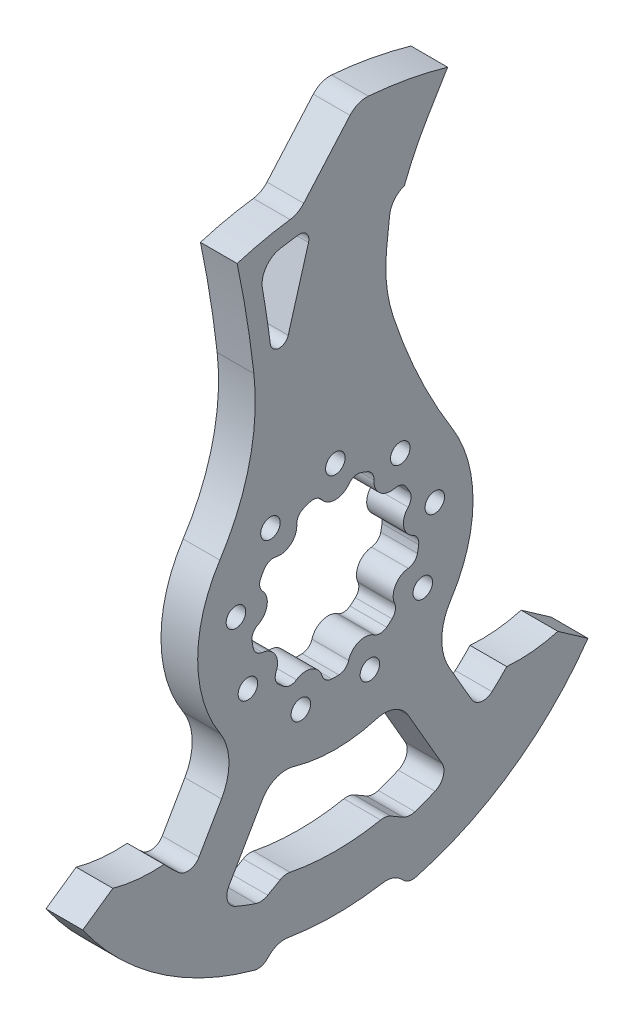
SolidWorks part; units mm, degrees
material "AR500"
ref_plane "Front Plane" through (0, 0, 0) normal (0, 0, 1) x (1, 0, 0)
ref_plane "Top Plane" through (0, 0, 0) normal (0, 1, 0) x (1, 0, 0)
ref_plane "Right Plane" through (0, 0, 0) normal (1, 0, 0) x (0, 0, -1)
other "Center of Mass"
sketch "Sketch1" plane through (0, 0, 0) normal (1, 0, 0) x (0, 0, -1)
  circle A0 centre (0, 0) radius 139.7 construction
  circle A1 centre (0, 0) radius 106.68 construction
  circle A2 centre (0, 0) radius 44.45 construction
  dimension "D1" = 279.4
  dimension "D2" = 33.02
  dimension "D3" = 88.9
sketch "Sketch2" plane through (0, 0, 0) normal (1, 0, 0) x (0, 0, -1)
  line L0 (0, 0) -> (38.858, 134.187) construction
  line L1 (38.858, 134.187) -> (32.2885, 123.3181)
  line L2 (0, 0) -> (0, 61.679) construction
  line L3 (7.5549, 139.4956) -> (-12.8644, 116.1296)
  line L4 (-33.9764, 111.7908) -> (-39.3372, 137.2171) construction
  line L5 (23.88, 106.192) -> (16.7676, 87.8077) construction
  line L6 (23.88, 106.192) -> (19.2337, 104.1379)
  line L7 (19.2337, 104.1379) -> (17.7417, 90.2907)
  line L8 (-33.9764, 111.7908) -> (-3.6464, 121.009) construction
  line L10 (0, -100.33) -> (0, 0) construction
  line L11 (-20.0866, -98.2987) -> (-25.4, -103.6121)
  line L16 (-49.9001, -64.1593) -> (-32.7957, -34.5337)
  line L17 (87.3871, -61.1891) -> (76.9839, -53.9047)
  line L18 (-87.3871, -61.1891) -> (-76.9839, -53.9047)
  line L19 (49.9001, -64.1593) -> (32.7957, -34.5337)
  line L24 (53.8815, -53.8815) -> (0, 0) construction
  line L25 (20.0866, -98.2987) -> (25.4, -103.6121)
  circle A0 centre (0, 0) radius 139.7 construction
  arc A1 (38.858, 134.187) -> (7.5549, 139.4956) centre (0, 0) ccw
  arc A2 (-12.8644, 116.1296) -> (-33.9764, 111.7908) centre (0, 0) ccw
  arc A3 (32.2885, 123.3181) -> (23.88, 106.192) centre (125.9607, 66.6999) ccw
  arc A4 (40.4523, 25.1346) -> (32.7957, -34.5337) centre (0, 0) cw
  circle A5 centre (0, 0) radius 44.45 construction
  arc A6 (19.9828, 69.006) -> (17.7417, 90.2907) centre (68.2493, 84.8485) cw
  arc A7 (-33.9764, 111.7908) -> (-28.182, 75.8993) centre (-406.7808, 33.191) cw
  arc A8 (-28.182, 75.8993) -> (-39.9622, 25.9068) centre (-103.9018, 67.3576) cw
  arc A9 (-39.9622, 25.9068) -> (-32.7957, -34.5337) centre (0, 0) ccw
  arc A10 (-87.3871, -61.1891) -> (-25.4, -103.6121) centre (0, 0) ccw
  circle A11 centre (0, 0) radius 106.68 construction
  arc A18 (-76.9839, -53.9047) -> (-59.2852, -55.6031) centre (-63.357, -4.9665) ccw
  arc A19 (-59.2852, -55.6031) -> (-49.9001, -64.1593) centre (0, 0) ccw
  arc A20 (-20.0866, -98.2987) -> (20.0866, -98.2987) centre (0, 0) ccw
  arc A21 (59.2852, -55.6031) -> (49.9001, -64.1593) centre (0, 0) cw
  arc A22 (76.9839, -53.9047) -> (59.2852, -55.6031) centre (63.357, -4.9665) cw
  arc A23 (87.3871, -61.1891) -> (25.4, -103.6121) centre (0, 0) cw
  arc A25 (19.9828, 69.006) -> (40.4523, 25.1346) centre (213.0489, 132.3758) ccw
  dimension "D4" = 22.86
  dimension "D11" = 95.25
  dimension "D13" = 50.8
  dimension "D14" = 381
  dimension "D16" = 76.2
  dimension "D19" = 6.35
  dimension "D21" = 55
  dimension "D26" = 17.78
  dimension "D22" = 25.4
  dimension "D23" = 50.8
  dimension "D27" = 12.7
  dimension "D29" = 203.2
  dimension "D1" = 15
  dimension "D2" = 16.15
  dimension "D3" = 10
  dimension "D5" = 31.75
  dimension "D6" = 12.7
  dimension "D7" = 31.75
  dimension "D8" = 5
  dimension "D9" = 45
  dimension "D10" = 10
  dimension "D12" = 5.08
  dimension "D15" = 85
  dimension "D17" = 76.2
  dimension "D18" = 25.4
  dimension "D20" = 45
  dimension "D24" = 12.7
  dimension "D25" = 45
  dimension "D28" = 30
extrude "Boss-Extrude1" add sketch "Sketch2" along normal mid plane 12.7
sketch "Sketch3" plane through (6.35, 0, 0) normal (1, 0, 0) x (0, 0, -1)
  line L1 (-9.2851, 105.7206) -> (-16.3113, 81.4575)
  line L2 (17.7417, 90.2907) -> (19.2337, 104.1379) construction
  line L3 (-3.258, 62.2657) -> (5.5274, 106.8394) construction
  line L4 (19.2337, 104.1379) -> (-8.1789, 109.5409) construction
  arc A0 (-12.8644, 116.1296) -> (-33.9764, 111.7908) centre (0, 0) ccw construction
  arc A1 (-28.182, 75.8993) -> (-33.9764, 111.7908) centre (-406.7808, 33.191) ccw construction
  arc A2 (-9.2851, 105.7206) -> (-12.6998, 109.7577) centre (-12.3348, 106.6038) ccw
  arc A3 (-12.8644, 116.1296) -> (-33.9764, 111.7908) centre (0, 0) ccw construction
  arc A4 (-28.182, 75.8993) -> (-33.9764, 111.7908) centre (-406.7808, 33.191) ccw construction
  arc A5 (-12.6998, 109.7577) -> (-26.5758, 107.2463) centre (0, 0) ccw
  arc A6 (-22.5107, 81.941) -> (-26.5758, 107.2463) centre (-406.7808, 33.191) ccw
  arc A7 (-21.8721, 76.6111) -> (-26.5758, 107.2463) centre (-406.7808, 33.191) ccw construction
  arc A8 (-12.1653, 109.8182) -> (-26.5758, 107.2463) centre (0, 0) ccw construction
  arc A14 (-22.5107, 81.941) -> (-16.3113, 81.4575) centre (-19.361, 82.3406) ccw
  point P18 (19.2337, 104.1379)
  dimension "D5" = 3.175
  dimension "D7" = 3.175
  dimension "D3" = 10
  dimension "D4" = 27.94
  dimension "D1" = 6.35
extrude "Cut-Extrude1" cut sketch "Sketch3" against normal through all
fillet "Fillet1" radius 7.62 6 edges at (0, 104.1379, -19.2337) (0, 107.2463, 26.5758) (0, 139.4956, -7.5549) (0, 116.1296, 12.8644) (0, -98.2987, -20.0866) (0, -98.2987, 20.0866)
fillet "Fillet4" radius 19.05 2 edges at (0, -34.5337, -32.7957) (0, -34.5337, 32.7957)
fillet "Fillet2" radius 4.572 4 edges at (0, -103.6121, 25.4) (0, -103.6121, -25.4) (0, -64.1593, -49.9001) (0, -64.1593, 49.9001)
sketch "Sketch4" plane through (6.35, 0, 0) normal (1, 0, 0) x (0, 0, -1)
  line L0 (-21.1843, -46.1721) -> (-39.646, -78.1487)
  line L1 (-39.3687, -45.9185) -> (-47.1846, -59.4559) construction
  line L2 (0, -81.28) -> (0, -50.8)
  line L3 (-25.3274, -83.8901) -> (-17.5035, -79.373)
  line L4 (-11.6185, -94.3061) -> (-25.8749, -102.5371) construction
  arc A0 (-39.646, -78.1487) -> (-25.3274, -83.8901) centre (0, 0) ccw
  arc A1 (0, -50.8) -> (-21.1843, -46.1721) centre (0, 0) cw
  circle A2 centre (0, 0) radius 44.45 construction
  circle A3 centre (0, 0) radius 106.68 construction
  arc A4 (-17.5035, -79.373) -> (0, -81.28) centre (0, 0) ccw
  arc A5 (-16.2916, -98.9984) -> (16.2916, -98.9984) centre (0, 0) ccw construction
  arc A6 (-87.3871, -61.1891) -> (-27.9851, -102.9439) centre (0, 0) ccw construction
  arc A7 (-16.2916, -98.9984) -> (-22.9171, -101.1292) centre (-17.5289, -106.5173) ccw construction
  dimension "D1" = 50.8
  dimension "D3" = 19.05
  dimension "D4" = 19.05
  dimension "D2" = 15.875
  dimension "D5" = 30
  dimension "D6" = 15.875
extrude "Cut-Extrude2" cut sketch "Sketch4" against normal through all
mirror "Mirror1" about plane through (-6.35, -81.28, 0) normal (0, 0, -1) of "Cut-Extrude2"
fillet "Fillet3" radius 5.08 6 edges at (0, -78.1487, -39.646) (0, -83.8901, -25.3274) (0, -79.373, -17.5035) (0, -79.373, 17.5035) (0, -83.8901, 25.3274) (0, -78.1487, 39.646)
fillet "Fillet5" radius 9.525 2 edges at (0, -46.1721, -21.1843) (0, -46.1721, 21.1843)
ref_axis "Axis2" through (-6.985, 0, 0) along (1, 0, 0)
sketch "Sketch5" plane through (-6.35, 0, 0) normal (-1, 0, 0) x (0, 0, 1)
  arc A36 (-24.1266, 15.3113) -> (-25.3233, 13.2386) centre (0, 0) ccw construction
  arc A37 (-20.6919, 16.6942) -> (-24.1266, 15.3113) centre (-21.4459, 13.6101) ccw construction
  arc A38 (-20.6919, 16.6942) -> (-12.8475, 23.2765) centre (-19.184, 22.8626) ccw construction
  arc A39 (-10.8892, 26.4189) -> (-12.8475, 23.2765) centre (-9.6793, 23.4834) ccw construction
  arc A40 (-8.6401, 27.2374) -> (-10.8892, 26.4189) centre (0, 0) ccw construction
  arc A41 (-5.1201, 26.089) -> (-8.6401, 27.2374) centre (-7.6801, 24.2111) ccw construction
  arc A42 (-5.1201, 26.089) -> (5.1201, 26.089) centre (0, 29.845) ccw construction
  arc A43 (8.6401, 27.2374) -> (5.1201, 26.089) centre (7.6801, 24.2111) ccw construction
  arc A44 (10.8892, 26.4189) -> (8.6401, 27.2374) centre (0, 0) ccw construction
  arc A45 (12.8475, 23.2765) -> (10.8892, 26.4189) centre (9.6793, 23.4834) ccw construction
  arc A46 (12.8475, 23.2765) -> (20.6919, 16.6942) centre (19.184, 22.8626) ccw construction
  arc A47 (24.1266, 15.3113) -> (20.6919, 16.6942) centre (21.4459, 13.6101) ccw construction
  arc A48 (25.3233, 13.2386) -> (24.1266, 15.3113) centre (0, 0) ccw construction
  arc A49 (24.8036, 9.5726) -> (25.3233, 13.2386) centre (22.5096, 11.7677) ccw construction
  arc A50 (24.8036, 9.5726) -> (26.5818, -0.512) centre (29.3916, 5.1825) ccw construction
  arc A51 (28.324, -3.7791) -> (26.5818, -0.512) centre (25.1769, -3.3592) ccw construction
  arc A52 (27.9084, -6.1361) -> (28.324, -3.7791) centre (0, 0) ccw construction
  arc A53 (25.1538, -8.6104) -> (27.9084, -6.1361) centre (24.8075, -5.4543) ccw construction
  arc A54 (25.1538, -8.6104) -> (20.0337, -17.4786) centre (25.8465, -14.9225) ccw construction
  arc A55 (19.2682, -21.1013) -> (20.0337, -17.4786) centre (17.1273, -18.7567) ccw construction
  arc A56 (17.4348, -22.6397) -> (19.2682, -21.1013) centre (0, 0) ccw construction
  arc A57 (13.7343, -22.7645) -> (17.4348, -22.6397) centre (15.4976, -20.1242) ccw construction
  arc A58 (13.7343, -22.7645) -> (4.1117, -26.2669) centre (10.2076, -28.0451) ccw construction
  arc A59 (1.1967, -28.5499) -> (4.1117, -26.2669) centre (1.0637, -25.3777) ccw construction
  arc A60 (-1.1967, -28.5499) -> (1.1967, -28.5499) centre (0, 0) ccw construction
  arc A61 (-4.1117, -26.2669) -> (-1.1967, -28.5499) centre (-1.0637, -25.3777) ccw construction
  arc A62 (-4.1117, -26.2669) -> (-13.7343, -22.7645) centre (-10.2076, -28.0451) ccw construction
  arc A63 (-17.4348, -22.6397) -> (-13.7343, -22.7645) centre (-15.4976, -20.1242) ccw construction
  arc A64 (-19.2682, -21.1013) -> (-17.4348, -22.6397) centre (0, 0) ccw construction
  arc A65 (-20.0337, -17.4786) -> (-19.2682, -21.1013) centre (-17.1273, -18.7567) ccw construction
  arc A66 (-20.0337, -17.4786) -> (-25.1538, -8.6104) centre (-25.8465, -14.9225) ccw construction
  arc A67 (-27.9084, -6.1361) -> (-25.1538, -8.6104) centre (-24.8075, -5.4543) ccw construction
  arc A68 (-28.324, -3.7791) -> (-27.9084, -6.1361) centre (0, 0) ccw construction
  arc A69 (-26.5818, -0.512) -> (-28.324, -3.7791) centre (-25.1769, -3.3592) ccw construction
  arc A70 (-26.5818, -0.512) -> (-24.8036, 9.5726) centre (-29.3916, 5.1825) ccw construction
  arc A71 (-25.3233, 13.2386) -> (-24.8036, 9.5726) centre (-22.5096, 11.7677) ccw construction
  arc A146 (-24.1266, 15.3113) -> (-25.3233, 13.2386) centre (0, 0) ccw construction
  arc A147 (-20.6919, 16.6942) -> (-24.1266, 15.3113) centre (-21.4459, 13.6101) ccw construction
  arc A148 (-20.6919, 16.6942) -> (-12.8475, 23.2765) centre (-19.184, 22.8626) ccw construction
  arc A149 (-10.8892, 26.4189) -> (-12.8475, 23.2765) centre (-9.6793, 23.4834) ccw construction
  arc A150 (-8.6401, 27.2374) -> (-10.8892, 26.4189) centre (0, 0) ccw construction
  arc A151 (-5.1201, 26.089) -> (-8.6401, 27.2374) centre (-7.6801, 24.2111) ccw construction
  arc A152 (-5.1201, 26.089) -> (5.1201, 26.089) centre (0, 29.845) ccw construction
  arc A153 (8.6401, 27.2374) -> (5.1201, 26.089) centre (7.6801, 24.2111) ccw construction
  arc A154 (10.8892, 26.4189) -> (8.6401, 27.2374) centre (0, 0) ccw construction
  arc A155 (12.8475, 23.2765) -> (10.8892, 26.4189) centre (9.6793, 23.4834) ccw construction
  arc A156 (12.8475, 23.2765) -> (20.6919, 16.6942) centre (19.184, 22.8626) ccw construction
  arc A157 (24.1266, 15.3113) -> (20.6919, 16.6942) centre (21.4459, 13.6101) ccw construction
  arc A158 (25.3233, 13.2386) -> (24.1266, 15.3113) centre (0, 0) ccw construction
  arc A159 (24.8036, 9.5726) -> (25.3233, 13.2386) centre (22.5096, 11.7677) ccw construction
  arc A160 (24.8036, 9.5726) -> (26.5818, -0.512) centre (29.3916, 5.1825) ccw construction
  arc A161 (28.324, -3.7791) -> (26.5818, -0.512) centre (25.1769, -3.3592) ccw construction
  arc A162 (27.9084, -6.1361) -> (28.324, -3.7791) centre (0, 0) ccw construction
  arc A163 (25.1538, -8.6104) -> (27.9084, -6.1361) centre (24.8075, -5.4543) ccw construction
  arc A164 (25.1538, -8.6104) -> (20.0337, -17.4786) centre (25.8465, -14.9225) ccw construction
  arc A165 (19.2682, -21.1013) -> (20.0337, -17.4786) centre (17.1273, -18.7567) ccw construction
  arc A166 (17.4348, -22.6397) -> (19.2682, -21.1013) centre (0, 0) ccw construction
  arc A167 (13.7343, -22.7645) -> (17.4348, -22.6397) centre (15.4976, -20.1242) ccw construction
  arc A168 (13.7343, -22.7645) -> (4.1117, -26.2669) centre (10.2076, -28.0451) ccw construction
  arc A169 (1.1967, -28.5499) -> (4.1117, -26.2669) centre (1.0637, -25.3777) ccw construction
  arc A170 (-1.1967, -28.5499) -> (1.1967, -28.5499) centre (0, 0) ccw construction
  arc A171 (-4.1117, -26.2669) -> (-1.1967, -28.5499) centre (-1.0637, -25.3777) ccw construction
  arc A172 (-4.1117, -26.2669) -> (-13.7343, -22.7645) centre (-10.2076, -28.0451) ccw construction
  arc A173 (-17.4348, -22.6397) -> (-13.7343, -22.7645) centre (-15.4976, -20.1242) ccw construction
  arc A174 (-19.2682, -21.1013) -> (-17.4348, -22.6397) centre (0, 0) ccw construction
  arc A175 (-20.0337, -17.4786) -> (-19.2682, -21.1013) centre (-17.1273, -18.7567) ccw construction
  arc A176 (-20.0337, -17.4786) -> (-25.1538, -8.6104) centre (-25.8465, -14.9225) ccw construction
  arc A177 (-27.9084, -6.1361) -> (-25.1538, -8.6104) centre (-24.8075, -5.4543) ccw construction
  arc A178 (-28.324, -3.7791) -> (-27.9084, -6.1361) centre (0, 0) ccw construction
  arc A179 (-26.5818, -0.512) -> (-28.324, -3.7791) centre (-25.1769, -3.3592) ccw construction
  arc A180 (-26.5818, -0.512) -> (-24.8036, 9.5726) centre (-29.3916, 5.1825) ccw construction
  arc A181 (-25.3233, 13.2386) -> (-24.8036, 9.5726) centre (-22.5096, 11.7677) ccw construction
  arc A182 (-24.5555, 15.5835) -> (-25.7735, 13.474) centre (0, 0) ccw
  arc A183 (-25.7735, 13.474) -> (-25.1706, 9.2214) centre (-22.5096, 11.7677) ccw
  arc A184 (-26.8066, -0.0564) -> (-25.1706, 9.2214) centre (-29.3916, 5.1825) ccw
  arc A185 (-26.8066, -0.0564) -> (-28.8275, -3.8463) centre (-25.1769, -3.3592) ccw
  arc A186 (-28.8275, -3.8463) -> (-28.4045, -6.2452) centre (0, 0) ccw
  arc A187 (-28.4045, -6.2452) -> (-25.2092, -9.1154) centre (-24.8075, -5.4543) ccw
  arc A188 (-20.4988, -17.2742) -> (-25.2092, -9.1154) centre (-25.8465, -14.9225) ccw
  arc A189 (-20.4988, -17.2742) -> (-19.6108, -21.4764) centre (-17.1273, -18.7567) ccw
  arc A190 (-19.6108, -21.4764) -> (-17.7448, -23.0422) centre (0, 0) ccw
  arc A191 (-17.7448, -23.0422) -> (-13.4521, -23.187) centre (-15.4976, -20.1242) ccw
  arc A192 (-4.5993, -26.4091) -> (-13.4521, -23.187) centre (-10.2076, -28.0451) ccw
  arc A193 (-4.5993, -26.4091) -> (-1.2179, -29.0575) centre (-1.0637, -25.3777) ccw
  arc A194 (-1.2179, -29.0575) -> (1.2179, -29.0575) centre (0, 0) ccw
  arc A195 (1.2179, -29.0575) -> (4.5993, -26.4091) centre (1.0637, -25.3777) ccw
  arc A196 (13.4521, -23.187) -> (4.5993, -26.4091) centre (10.2076, -28.0451) ccw
  arc A197 (13.4521, -23.187) -> (17.7448, -23.0422) centre (15.4976, -20.1242) ccw
  arc A198 (17.7448, -23.0422) -> (19.6108, -21.4764) centre (0, 0) ccw
  arc A199 (19.6108, -21.4764) -> (20.4988, -17.2742) centre (17.1273, -18.7567) ccw
  arc A200 (25.2092, -9.1154) -> (20.4988, -17.2742) centre (25.8465, -14.9225) ccw
  arc A201 (25.2092, -9.1154) -> (28.4045, -6.2452) centre (24.8075, -5.4543) ccw
  arc A202 (28.4045, -6.2452) -> (28.8275, -3.8463) centre (0, 0) ccw
  arc A203 (28.8275, -3.8463) -> (26.8066, -0.0564) centre (25.1769, -3.3592) ccw
  arc A204 (25.1706, 9.2214) -> (26.8066, -0.0564) centre (29.3916, 5.1825) ccw
  arc A205 (25.1706, 9.2214) -> (25.7735, 13.474) centre (22.5096, 11.7677) ccw
  arc A206 (25.7735, 13.474) -> (24.5555, 15.5835) centre (0, 0) ccw
  arc A207 (24.5555, 15.5835) -> (20.5713, 17.1877) centre (21.4459, 13.6101) ccw
  arc A208 (13.3544, 23.2434) -> (20.5713, 17.1877) centre (19.184, 22.8626) ccw
  arc A209 (13.3544, 23.2434) -> (11.0827, 26.8885) centre (9.6793, 23.4834) ccw
  arc A210 (11.0827, 26.8885) -> (8.7937, 27.7217) centre (0, 0) ccw
  arc A211 (8.7937, 27.7217) -> (4.7105, 26.3895) centre (7.6801, 24.2111) ccw
  arc A212 (-4.7105, 26.3895) -> (4.7105, 26.3895) centre (0, 29.845) ccw
  arc A213 (-4.7105, 26.3895) -> (-8.7937, 27.7217) centre (-7.6801, 24.2111) ccw
  arc A214 (-8.7937, 27.7217) -> (-11.0827, 26.8885) centre (0, 0) ccw
  arc A215 (-11.0827, 26.8885) -> (-13.3544, 23.2434) centre (-9.6793, 23.4834) ccw
  arc A216 (-20.5713, 17.1877) -> (-13.3544, 23.2434) centre (-19.184, 22.8626) ccw
  arc A217 (-20.5713, 17.1877) -> (-24.5555, 15.5835) centre (-21.4459, 13.6101) ccw
  dimension "D1" = 0.508
extrude "Cut-Extrude4" cut sketch "Sketch5" against normal through all
hole_wizard "1/4 Clearance Hole1" positions "Sketch6" profile "Sketch8" hole size "1/4" standard "ANSI Inch" end condition through all
sketch "Sketch6" plane through (6.35, 0, 0) normal (1, 0, 0) x (0, 0, -1)
  point P0 (0, 34.925)
sketch "Sketch8" plane through (6.35, 34.925, 0) normal (0, 1, 0) x (0, 0, -1)
  line L0 (0, 0) -> (0, 12.7)
  line L1 (0, 12.7) -> (3.3782, 12.7)
  line L2 (3.3782, 12.7) -> (3.3782, 0)
  line L5 (3.3782, 0) -> (0, 0)
  line L11 (0, -6.35) -> (0, 107.95) construction
  dimension "Thru Hole Dia." = 6.7564
  dimension "Thru Hole Depth" = 12.7
pattern_circular "CirPattern1" count 9 over 360 about axis through (-6.985, 0, 0) along (1, 0, 0) of "1/4 Clearance Hole1"
